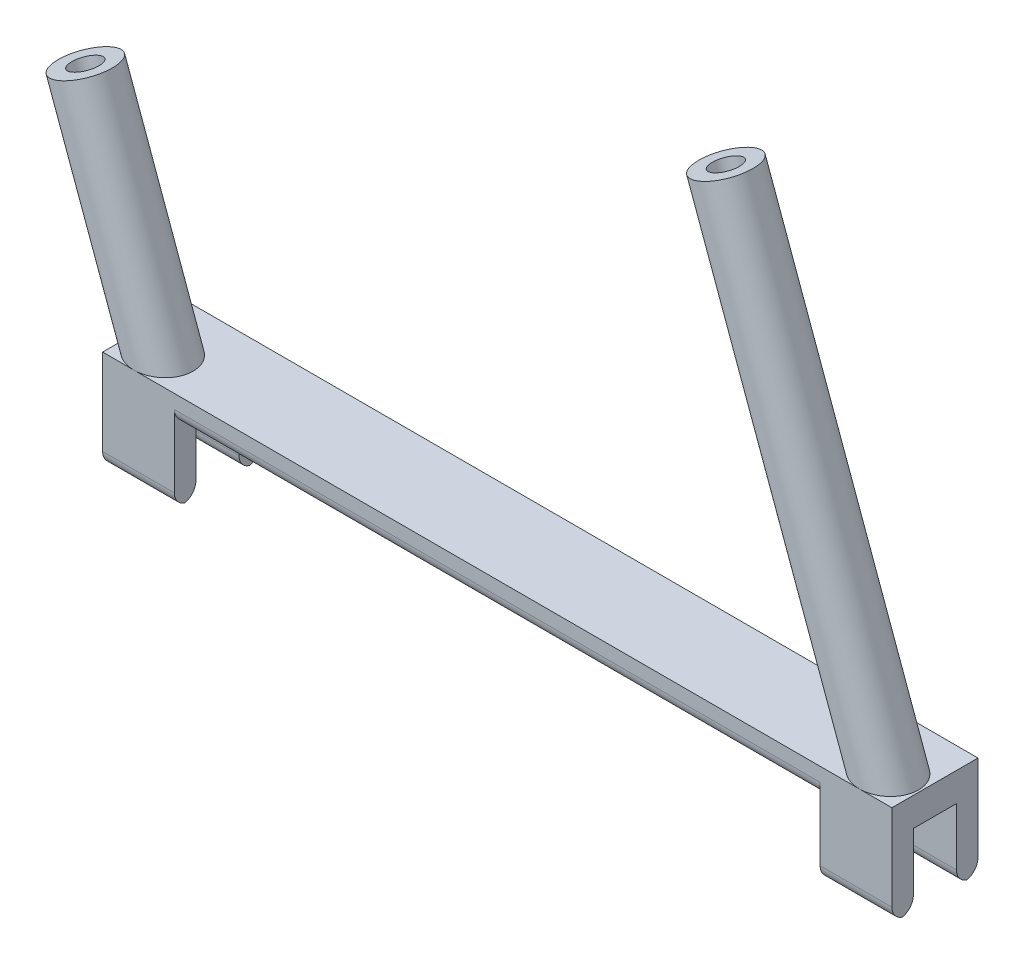
SolidWorks part; units mm, degrees
ref_plane "Plan de face" through (0, 0, 0) normal (0, 0, 1) x (1, 0, 0)
ref_plane "Plan de dessus" through (0, 0, 0) normal (0, 1, 0) x (1, 0, 0)
ref_plane "Plan de droite" through (0, 0, 0) normal (1, 0, 0) x (0, 0, -1)
sketch "Esquisse1" plane through (0, 0, 0) normal (0, 0, 1) x (1, 0, 0)
  line L1 (0, 0) -> (110, 0)
  line L2 (0, 0) -> (0, 14)
  line L3 (0, 14) -> (110, 14)
  line L4 (110, 0) -> (110, 14)
  dimension "D1" = 110
  dimension "D2" = 14
extrude "Boss.-Extru.1" add sketch "Esquisse1" along normal blind 12
sketch "Esquisse2" plane through (0, 0, 0) normal (-1, 0, 0) x (0, 0, 1)
  line L0 (12, 0) -> (0, 0) construction
  line L1 (3, 0) -> (9, 0)
  line L2 (3, 0) -> (3, 10)
  line L3 (3, 10) -> (9, 10)
  line L4 (9, 0) -> (9, 10)
  line L5 (0, 14) -> (0, 0) construction
  line L6 (12, 14) -> (12, 0) construction
  dimension "D1" = 3
  dimension "D2" = 3
  dimension "D3" = 10
extrude "Enlèv. mat.-Extru.1" cut sketch "Esquisse2" against normal through all
fillet "Congé1" radius 2 4 edges at (55, 0, 12) (55, 0, 9) (55, 0, 3) (55, 0, 0)
sketch "Esquisse3" plane through (0, 0, 12) normal (0, 0, 1) x (1, 0, 0)
  line L0 (0, 0.0635) -> (110, 0.0635) construction
  line L1 (10, 0.0635) -> (100, 0.0635)
  line L2 (10, 0.0635) -> (10, 10.0635)
  line L3 (10, 10.0635) -> (100, 10.0635)
  line L4 (100, 0.0635) -> (100, 10.0635)
  line L5 (0, 14) -> (0, 2) construction
  line L6 (110, 2) -> (110, 14) construction
  dimension "D1" = 10
  dimension "D2" = 10
  dimension "D3" = 10
extrude "Enlèv. mat.-Extru.2" cut sketch "Esquisse3" against normal blind 12
fillet "Congé2" radius 2 2 edges at (55, 10.0635, 0) (55, 10.0635, 12)
ref_plane "Plan1" through (-4.4995, 12.3623, 0) normal (-0.342, 0.9397, 0) x (0, 0, -1)
sketch "Esquisse6" plane through (-4.4995, 12.3623, 0) normal (-0.342, 0.9397, 0) x (0, 0, -1)
  line L1 (-12, 6.2522) -> (-12, -40.0914) construction
  line L2 (-12, -4.7883) -> (0, -4.7883) construction
  circle A0 centre (-8, -8.8883) radius 2
  circle A1 centre (-8, -8.8883) radius 4
  circle A2 centre (-8, -103.8883) radius 2
  circle A3 centre (-8, -103.8883) radius 4
  dimension "D1" = 4
  dimension "D2" = 2
  dimension "D3" = 4
  dimension "D4" = 4.1
  dimension "D5" = 2
extrude "Boss.-Extru.2" add sketch "Esquisse6" along normal blind 30 and the other way up to next
